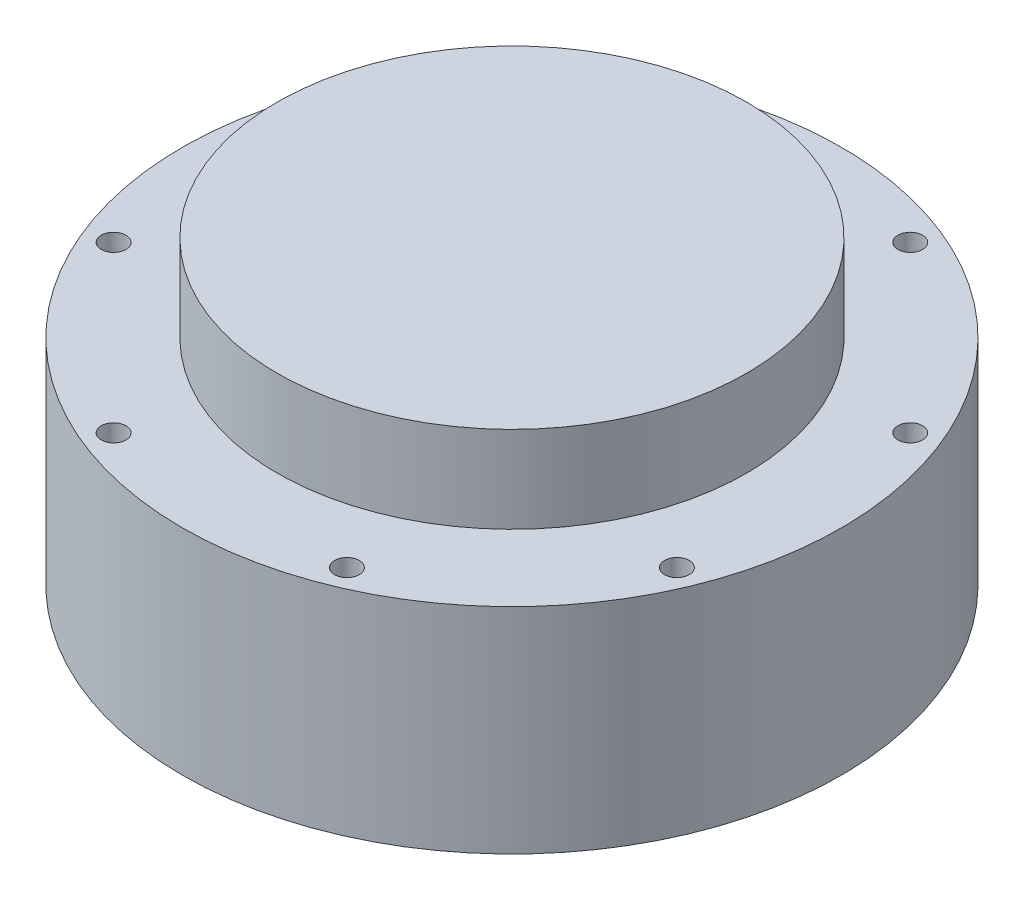
SolidWorks part; units mm, degrees
material "AISI 1020 钢，冷轧"
ref_plane "前视基准面" through (0, 0, 0) normal (0, 0, 1) x (1, 0, 0)
ref_plane "上视基准面" through (0, 0, 0) normal (0, 1, 0) x (1, 0, 0)
ref_plane "右视基准面" through (0, 0, 0) normal (1, 0, 0) x (0, 0, -1)
other "Configuration Table"
sketch "草图1" plane through (0, 0, 0) normal (0, 1, 0) x (1, 0, 0)
  circle A0 centre (0, 0) radius 40
  dimension "D1" = 80
extrude "凸台-拉伸1" add sketch "草图1" along normal blind 13 and the other way blind 13
sketch "草图2" plane through (0, 13, 0) normal (0, 1, 0) x (1, 0, 0)
  circle A0 centre (0, 0) radius 28.5
  dimension "D1" = 57
extrude "凸台-拉伸2" add sketch "草图2" along normal blind 10.5
sketch "草图3" plane through (0, -13, 0) normal (0, -1, 0) x (1, 0, 0)
  circle A0 centre (0, 0) radius 23.5
  dimension "D1" = 47
extrude "凸台-拉伸3" add sketch "草图3" along normal blind 2.8
sketch "草图4" plane through (0, -15.8, 0) normal (0, -1, 0) x (1, 0, 0)
  circle A0 centre (0, 0) radius 17
  dimension "D1" = 34
extrude "凸台-拉伸4" add sketch "草图4" along normal blind 0.7
sketch "草图5" plane through (0, 13, 0) normal (0, 1, 0) x (1, 0, 0)
  line L0 (-1000, 0) -> (49000, 0) construction
  line L1 (0, -1000) -> (0, 49000) construction
  line L2 (-707.1068, -707.1068) -> (34648.2323, 34648.2323) construction
  line L3 (14.1593, 34.1835) -> (34.1835, 14.1593) construction
  line L4 (34.1835, 14.1593) -> (34.1835, -14.1593) construction
  circle A0 centre (0, 0) radius 37 construction
  circle A1 centre (14.1593, 34.1835) radius 1.5
  circle A2 centre (34.1835, 14.1593) radius 1.5
  circle A3 centre (34.1835, -14.1593) radius 1.5
  circle A4 centre (14.1593, -34.1835) radius 1.5
  circle A5 centre (-14.1593, -34.1835) radius 1.5
  circle A6 centre (-34.1835, -14.1593) radius 1.5
  circle A7 centre (-34.1835, 14.1593) radius 1.5
  circle A8 centre (-14.1593, 34.1835) radius 1.5
  dimension "D1" = 74
  dimension "D2" = 3
  dimension "D3" = 45
extrude "切除-拉伸1" cut sketch "草图5" against normal blind 5
sketch "草图6" plane through (0, -13, -13) normal (0, 1, 0) x (1, 0, 0)
  line L0 (-1000, -13) -> (49000, -13) construction
  line L1 (0, -1000) -> (0, 49000) construction
  line L2 (-707.1068, -720.1068) -> (34648.2323, 34635.2323) construction
  line L3 (14.1593, 21.1835) -> (34.1835, 1.1593) construction
  line L4 (34.1835, 1.1593) -> (34.1835, -27.1593) construction
  circle A0 centre (0, -13) radius 37 construction
  circle A1 centre (14.1593, 21.1835) radius 1.5
  circle A2 centre (34.1835, 1.1593) radius 1.5
  circle A3 centre (34.1835, -27.1593) radius 1.5
  circle A4 centre (14.1593, -47.1835) radius 1.5
  circle A5 centre (-14.1593, -47.1835) radius 1.5
  circle A6 centre (-34.1835, -27.1593) radius 1.5
  circle A7 centre (-34.1835, 1.1593) radius 1.5
  circle A8 centre (-14.1593, 21.1835) radius 1.5
  dimension "D1" = 74
  dimension "D2" = 3
  dimension "D3" = 45
extrude "切除-拉伸3" cut sketch "草图6" along normal blind 5
sketch "草图7" plane through (0, -16.5, 0) normal (0, -1, 0) x (1, 0, 0)
  line L0 (0, -1000) -> (0, 49000) construction
  line L1 (-1000, 0) -> (49000, 0) construction
  line L2 (-6.25, 10.8253) -> (0, 0) construction
  circle A0 centre (0, 0) radius 12.5 construction
  circle A1 centre (-12.5, 0) radius 1.5
  circle A2 centre (-6.25, 10.8253) radius 1.5
  circle A3 centre (-6.25, -10.8253) radius 1.5
  circle A4 centre (6.25, -10.8253) radius 1.5
  circle A5 centre (12.5, 0) radius 1.5
  circle A6 centre (6.25, 10.8253) radius 1.5
  dimension "D1" = 25
  dimension "D2" = 3
  dimension "D3" = 3
  dimension "D4" = 60
extrude "切除-拉伸4" cut sketch "草图7" against normal blind 5
sketch "草图8" plane through (0, -16.5, 0) normal (0, -1, 0) x (1, 0, 0)
  line L0 (0, -1000) -> (0, 49000) construction
  line L1 (-8.8335, -5.1) -> (0, 0) construction
  circle A0 centre (0, 0) radius 10.2 construction
  circle A1 centre (0, 10.2) radius 2
  circle A2 centre (-8.8335, -5.1) radius 2
  circle A4 centre (8.8335, -5.1) radius 2
  dimension "D1" = 20.4
  dimension "D2" = 4
  dimension "D3" = 4
  dimension "D4" = 60
extrude "凸台-拉伸5" add sketch "草图8" along normal blind 3.5
